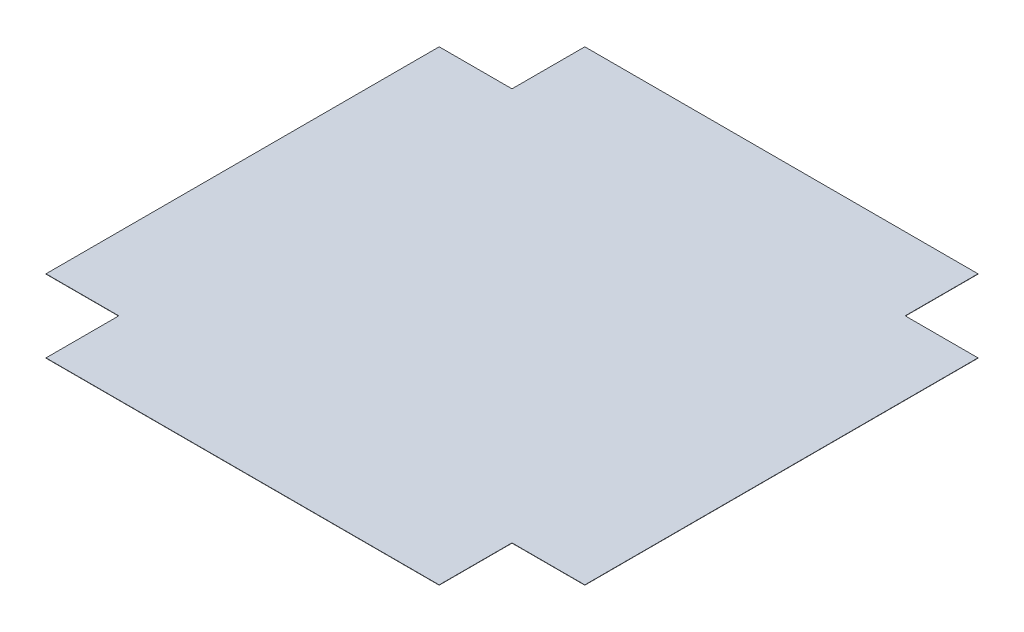
SolidWorks part; units mm, degrees
material "Corrugated Paper"
ref_plane "Front" through (0, 0, 0) normal (0, 0, 1) x (1, 0, 0)
ref_plane "Top" through (0, 0, 0) normal (0, 1, 0) x (1, 0, 0)
ref_plane "Right" through (0, 0, 0) normal (1, 0, 0) x (0, 0, -1)
ref_axis "X" through (-80.9, 0, 0) along (1, 0, 0)
ref_axis "Y" through (0, -50, 0) along (0, 1, 0)
ref_axis "Z" through (0, 0, -80.9) along (0, 0, 1)
sketch "Sketch1" plane through (0, 0, 0) normal (0, 1, 0) x (1, 0, 0)
  line L0 (-67.5, 92.5) -> (67.5, 92.5)
  line L1 (67.5, 92.5) -> (67.5, 67.5)
  line L2 (67.5, 67.5) -> (92.5, 67.5)
  line L3 (92.5, 67.5) -> (92.5, -67.5)
  line L4 (92.5, -67.5) -> (67.5, -67.5)
  line L5 (67.5, -67.5) -> (67.5, -92.5)
  line L6 (67.5, -92.5) -> (-67.5, -92.5)
  line L7 (-67.5, -92.5) -> (-67.5, -67.5)
  line L8 (-67.5, -67.5) -> (-92.5, -67.5)
  line L9 (-92.5, -67.5) -> (-92.5, 67.5)
  line L10 (-92.5, 67.5) -> (-67.5, 67.5)
  line L11 (-67.5, 67.5) -> (-67.5, 92.5)
  line L12 (-92.5, 0) -> (92.5, 0) construction
  line L13 (0, 92.5) -> (0, -92.5) construction
  dimension "D1" = 185
  dimension "D2" = 185
  dimension "D3" = 25
  dimension "D4" = 25
extrude "Boss-Extrude1" add sketch "Sketch1" along normal mid plane 0.1
sketch "Sketch2" plane through (0, -0.05, 0) normal (0, -1, 0) x (1, 0, 0)
  line L0 (67.5, 67.5) -> (43.5, 67.5)
  line L1 (67.5, 92.5) -> (67.5, 67.5) construction
  line L2 (43.5, 67.5) -> (43.5, 92.5)
  line L15 (-67.5, -67.5) -> (-67.5, -92.5)
  line L16 (-67.5, -92.5) -> (67.5, -92.5)
  line L17 (67.5, -92.5) -> (67.5, -67.5)
  line L18 (67.5, -67.5) -> (92.5, -67.5)
  line L19 (92.5, -67.5) -> (92.5, 67.5)
  line L20 (92.5, 67.5) -> (67.5, 67.5)
  line L21 (67.5, 67.5) -> (67.5, 92.5)
  line L22 (67.5, 92.5) -> (-67.5, 92.5)
  line L23 (-67.5, 92.5) -> (-67.5, 67.5)
  line L24 (-67.5, 67.5) -> (-92.5, 67.5)
  line L25 (-92.5, 67.5) -> (-92.5, -67.5)
  line L26 (-92.5, -67.5) -> (-67.5, -67.5)
  line L33 (67.5, 67.5) -> (67.5, 92.5)
  line L34 (67.5, 92.5) -> (43.5, 92.5)
  point P9 (37.5, 92.4099)
  line M21 (67.5, 67.5) -> (67.5, 92.5)
  line M22 (67.5, 92.5) -> (-67.5, 92.5)
  dimension "D1" = 0
  dimension "D2" = 24
extrude "Cut-Extrude1" [suppressed] cut sketch "Sketch2" against normal through all contours L2 L0 M21 M22
